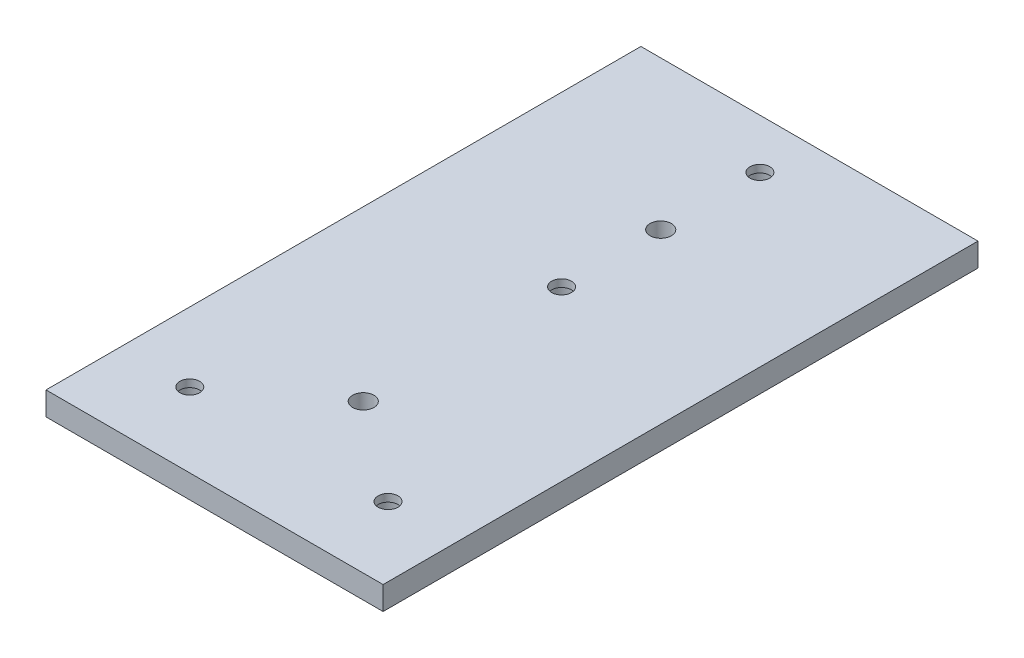
SolidWorks part; units mm, degrees
material "Melamine resin"
ref_plane "Front Plane" through (0, 0, 0) normal (0, 0, 1) x (1, 0, 0)
ref_plane "Top Plane" through (0, 0, 0) normal (0, 1, 0) x (1, 0, 0)
ref_plane "Right Plane" through (0, 0, 0) normal (1, 0, 0) x (0, 0, -1)
sketch "Sketch2" plane through (0, 0, 0) normal (0, 1, 0) x (1, 0, 0)
  line L1 (0, 0) -> (88.9, 0)
  line L2 (0, 0) -> (0, 152.4)
  line L3 (0, 152.4) -> (88.9, 152.4)
  line L10 (88.9, 152.4) -> (88.9, 0)
  dimension "D1" = 152.4
  dimension "D2" = 88.9
extrude "Boss-Extrude1" add sketch "Sketch2" along normal blind 5.9944 contours L3 L10 L1 L2
sketch "Sketch4" plane through (0, 5.9944, 0) normal (0, 1, 0) x (1, 0, 0)
  line L0 (0, 0) -> (0, 152.4) construction
  line L2 (45.72, 114.3) -> (45.72, 38.1) construction
  circle A0 centre (45.72, 114.3) radius 2.7305
  circle A1 centre (45.72, 38.1) radius 2.7305
  point P4 (0, 76.2)
  point P6 (45.72, 76.2)
  dimension "D3" = 5.461
  dimension "D4" = 5.461
  dimension "D1" = 76.2
  dimension "D2" = 45.72
extrude "Cut-Extrude2" cut sketch "Sketch4" against normal through all both
sketch "Sketch7" plane through (0, 5.9944, 0) normal (0, 1, 0) x (1, 0, 0)
  line L0 (0, 0) -> (16.256, 0) construction
  line L1 (0, 152.4) -> (2.54, 152.4)
  line L2 (0, 152.4) -> (0, 0)
  line L3 (0, 0) -> (2.54, 0)
  line L4 (2.54, 152.4) -> (2.54, 0)
  dimension "D1" = 2.54
extrude "Cut-Extrude3" cut sketch "Sketch7" against normal through all both
sketch "Sketch8" plane through (0, 5.9944, 0) normal (0, 1, 0) x (1, 0, 0)
  line L0 (45.72, 139.7) -> (45.72, 88.9) construction
  line L1 (20.32, 19.05) -> (71.12, 19.05) construction
  line L2 (2.54, 0) -> (88.9, 0) construction
  line L3 (2.54, 152.4) -> (88.9, 152.4) construction
  circle A0 centre (20.32, 19.05) radius 2.54
  circle A1 centre (71.12, 19.05) radius 2.54
  circle A2 centre (45.72, 88.9) radius 2.54
  circle A3 centre (45.72, 139.7) radius 2.54
  point P10 (45.72, 0)
  point P11 (45.72, 19.05)
  point P12 (39.4053, 134.8654)
  point P13 (44.4978, 139.7542)
  point P14 (0, 0)
  point P15 (45.3126, 136.9024)
  point P18 (45.72, 152.4)
  point P19 (45.72, 114.3)
  dimension "D1" = 5.08
  dimension "D2" = 5.08
  dimension "D3" = 5.08
  dimension "D4" = 5.08
  dimension "D5" = 50.8
  dimension "D6" = 50.8
  dimension "D7" = 19.05
  dimension "D8" = 12.7
extrude "Cut-Extrude4" cut sketch "Sketch8" against normal through all both and the other way through all
sketch "Sketch9" plane through (0, 0, 0) normal (0, -1, 0) x (1, 0, 0)
  circle A0 centre (20.32, -19.05) radius 3.683
  circle A1 centre (71.12, -19.05) radius 3.683
  circle A2 centre (45.72, -88.9) radius 3.683
  circle A3 centre (45.72, -139.7) radius 3.683
  dimension "D1" = 7.366
  dimension "D2" = 7.366
  dimension "D3" = 7.366
  dimension "D4" = 7.366
extrude "Cut-Extrude5" cut sketch "Sketch9" against normal blind 4.064
equation "\"threaded_insert_hole\"=0.1472"
equation "\"th\"=1.25249"
